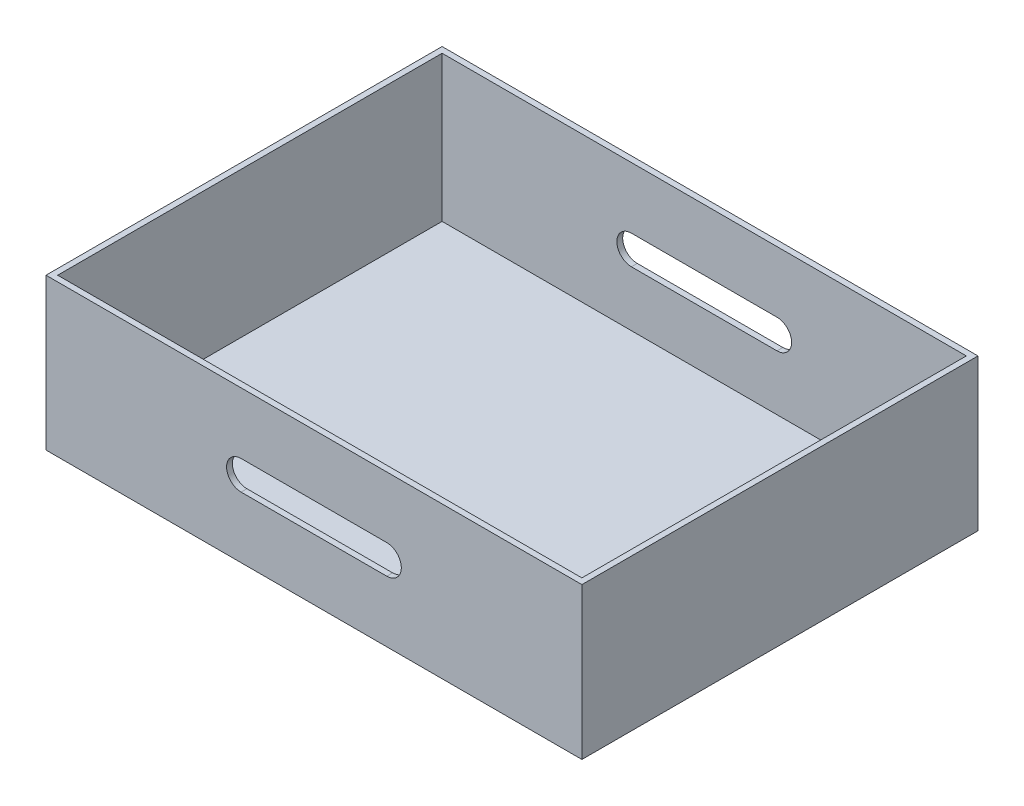
SolidWorks part; units mm, degrees
ref_plane "Plano frontal" through (0, 0, 0) normal (0, 0, 1) x (1, 0, 0)
ref_plane "Plano superior" through (0, 0, 0) normal (0, 1, 0) x (1, 0, 0)
ref_plane "Plano direito" through (0, 0, 0) normal (1, 0, 0) x (0, 0, -1)
sketch "Esboço1" plane through (0, 0, 0) normal (0, 1, 0) x (1, 0, 0)
  line L5 (-92, -68) -> (92, -68)
  line L6 (-92, -68) -> (-92, 68)
  line L7 (-92, 68) -> (92, 68)
  line L8 (92, -68) -> (92, 68)
  line L13 (-92, -68) -> (92, 68) construction
  line L14 (-92, 68) -> (92, -68) construction
  point P0 (0, 0)
  dimension "D1" = 184
  dimension "D2" = 136
extrude "Ressalto-extrusão1" add sketch "Esboço1" along normal blind 2
sketch "Esboço2" plane through (0, 2, 0) normal (0, 1, 0) x (1, 0, 0)
  line L1 (-90, -66) -> (90, -66)
  line L2 (-90, -66) -> (-90, 66)
  line L3 (-90, 66) -> (90, 66)
  line L4 (90, -66) -> (90, 66)
  line L5 (-90, -66) -> (90, 66) construction
  line L6 (-90, 66) -> (90, -66) construction
  point P0 (0, 0)
  dimension "D1" = 180
  dimension "D2" = 132
extrude "Extrusão-Fina1" add sketch "Esboço2" along normal blind 50 thin thin type one direction wall 2
sketch "Esboço3" plane through (0, 0, 68) normal (0, 0, 1) x (1, 0, 0)
  line L0 (0, 0) -> (0, 52) construction
  line L1 (-92, 0) -> (92, 0) construction
  line L2 (-92, 52) -> (92, 52) construction
  line L3 (92, 26) -> (-92, 26) construction
  line L4 (92, 52) -> (92, 0) construction
  line L5 (-92, 52) -> (-92, 0) construction
  line L6 (-25, 26) -> (25, 26) construction
  line L7 (-25, 31) -> (25, 31)
  line L8 (-25, 21) -> (25, 21)
  arc A0 (-25, 31) -> (-25, 21) centre (-25, 26) ccw
  arc A1 (25, 21) -> (25, 31) centre (25, 26) ccw
  point P14 (0, 26)
  dimension "D1" = 50
  dimension "D2" = 10
extrude "Corte-extrusão1" cut sketch "Esboço3" against normal through all
